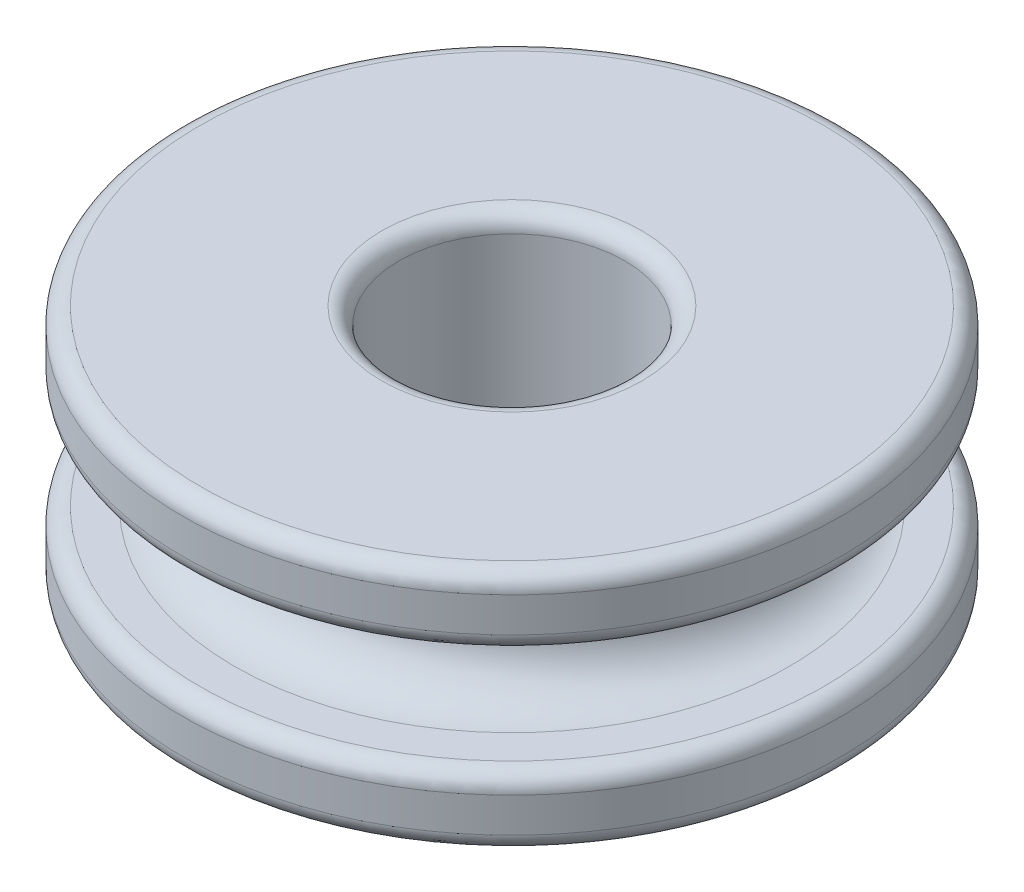
SolidWorks part; units mm, degrees
ref_plane "Front Plane" through (0, 0, 0) normal (0, 0, 1) x (1, 0, 0)
ref_plane "Top Plane" through (0, 0, 0) normal (0, 1, 0) x (1, 0, 0)
ref_plane "Right Plane" through (0, 0, 0) normal (1, 0, 0) x (0, 0, -1)
sketch "Sketch1" plane through (0, 0, 0) normal (0, 0, 1) x (1, 0, 0)
  line L0 (-1.625, 0) -> (6.375, 0) construction
  line L1 (-1.625, -3.5) -> (1.625, -3.5) construction
  line L2 (-1.625, -3.5) -> (-1.625, 3.5) construction
  line L3 (-1.625, 3.5) -> (1.625, 3.5) construction
  line L4 (1.625, -3.5) -> (1.625, 3.5)
  line L5 (-1.625, -3.5) -> (1.625, 3.5) construction
  line L6 (-1.625, 3.5) -> (1.625, -3.5) construction
  line L7 (6.375, 1.5) -> (6.375, -1.5) construction
  line L8 (1.625, 3.5) -> (6.375, 3.5)
  line L9 (1.625, 3.5) -> (1.625, -3.5)
  line L10 (1.625, -3.5) -> (6.375, -3.5)
  line L12 (6.375, -1) -> (6.375, -1.5)
  line L16 (6.375, 1.5) -> (7.875, 1.5)
  line L20 (6.375, 3.5) -> (7.875, 3.5)
  line L21 (7.875, 1.5) -> (7.875, 3.5)
  line L22 (6.375, -1.5) -> (7.875, -1.5)
  line L24 (6.375, -3.5) -> (7.875, -3.5)
  line L25 (7.875, -1.5) -> (7.875, -3.5)
  arc A7 (6.375, 1.5) -> (6.375, -1.5) centre (6.375, 0) ccw
  point P0 (0, 0)
  point P18 (3.2, 0)
  dimension "D4" = 4.75
  dimension "D5" = 3
  dimension "D1" = 3.25
  dimension "D2" = 7
  dimension "D3" = 8
  dimension "D6" = 1.5
revolve "Revolve1" add sketch "Sketch1" angle 360 about L2 region at (4.353, 0, 0)
fillet "Fillet1" radius 0.5 6 edges at (-1.625, -3.5, -3.25) (-1.625, 3.5, -3.25) (-1.625, 1.5, -9.5) (-1.625, -1.5, -9.5) (-1.625, 3.5, -9.5) (-1.625, -3.5, -9.5)
